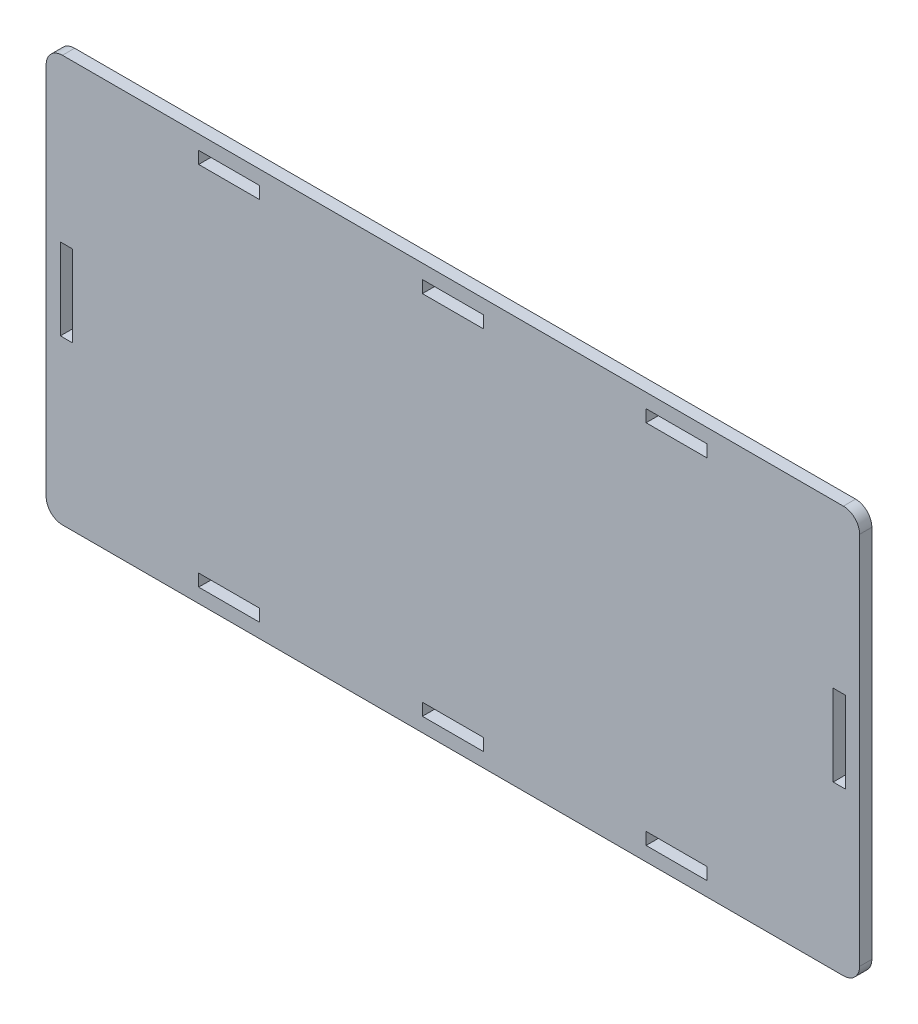
SolidWorks part; units mm, degrees
ref_plane "Front Plane" through (0, 0, 0) normal (0, 0, 1) x (1, 0, 0)
ref_plane "Top Plane" through (0, 0, 0) normal (0, 1, 0) x (1, 0, 0)
ref_plane "Right Plane" through (0, 0, 0) normal (1, 0, 0) x (0, 0, -1)
sketch "Sketch1" plane through (0, 0, 0) normal (0, 0, 1) x (1, 0, 0)
  line L1 (-96, 50) -> (96, 50)
  line L2 (-100, 46) -> (-100, -46)
  line L3 (-96, -50) -> (96, -50)
  line L4 (100, 46) -> (100, -46)
  line L5 (-100, 50) -> (100, -50) construction
  line L6 (-100, -50) -> (100, 50) construction
  arc A0 (96, 50) -> (100, 46) centre (96, 46) cw
  arc A1 (100, -46) -> (96, -50) centre (96, -46) cw
  arc A2 (-96, -50) -> (-100, -46) centre (-96, -46) cw
  arc A3 (-100, 46) -> (-96, 50) centre (-96, 46) cw
  point P0 (0, 0)
  dimension "D3" = 4
  dimension "D1" = 200
  dimension "D2" = 100
extrude "Boss-Extrude2" add sketch "Sketch1" along normal blind 3
sketch "Sketch3" plane through (0, 0, 3) normal (0, 0, 1) x (1, 0, 0)
  line L0 (0, 50) -> (0, -50) construction
  line L1 (-95, 45) -> (95, 45) construction
  line L2 (-95, 45) -> (-95, -45) construction
  line L3 (-95, -45) -> (95, -45) construction
  line L4 (95, 45) -> (95, -45) construction
  line L5 (-95, 45) -> (95, -45) construction
  line L6 (-95, -45) -> (95, 45) construction
  line L7 (-62.5, 46.5) -> (-47.5, 46.5)
  line L8 (-62.5, 46.5) -> (-62.5, 43.5)
  line L9 (-62.5, 43.5) -> (-47.5, 43.5)
  line L10 (-47.5, 46.5) -> (-47.5, 43.5)
  line L11 (-62.5, 46.5) -> (-47.5, 43.5) construction
  line L12 (-62.5, 43.5) -> (-47.5, 46.5) construction
  line L13 (96, 50) -> (-96, 50) construction
  line L14 (-96, -50) -> (96, -50) construction
  line L15 (100, 0) -> (-100, 0) construction
  line L16 (100, -46) -> (100, 46) construction
  line L17 (-100, 46) -> (-100, -46) construction
  line L22 (62.5, 43.5) -> (47.5, 43.5)
  line L23 (-7.5, 46.5) -> (7.5, 46.5)
  line L24 (-7.5, 46.5) -> (-7.5, 43.5)
  line L25 (-7.5, 43.5) -> (7.5, 43.5)
  line L26 (7.5, 46.5) -> (7.5, 43.5)
  line L27 (-7.5, 46.5) -> (7.5, 43.5) construction
  line L28 (-7.5, 43.5) -> (7.5, 46.5) construction
  line L29 (-96.5, 10) -> (-93.5, 10)
  line L30 (-96.5, 10) -> (-96.5, -10)
  line L31 (-96.5, -10) -> (-93.5, -10)
  line L32 (-93.5, 10) -> (-93.5, -10)
  line L33 (-96.5, 10) -> (-93.5, -10) construction
  line L34 (-96.5, -10) -> (-93.5, 10) construction
  line L35 (47.5, 46.5) -> (47.5, 43.5)
  line L36 (62.5, 46.5) -> (47.5, 46.5)
  line L37 (62.5, 46.5) -> (62.5, 43.5)
  line L38 (-62.5, -43.5) -> (-47.5, -43.5)
  line L39 (-47.5, -46.5) -> (-47.5, -43.5)
  line L40 (-62.5, -46.5) -> (-47.5, -46.5)
  line L41 (-62.5, -46.5) -> (-62.5, -43.5)
  line L42 (-7.5, -43.5) -> (7.5, -43.5)
  line L43 (7.5, -46.5) -> (7.5, -43.5)
  line L44 (-7.5, -46.5) -> (7.5, -46.5)
  line L45 (-7.5, -46.5) -> (-7.5, -43.5)
  line L46 (62.5, -46.5) -> (62.5, -43.5)
  line L47 (62.5, -46.5) -> (47.5, -46.5)
  line L48 (47.5, -46.5) -> (47.5, -43.5)
  line L49 (62.5, -43.5) -> (47.5, -43.5)
  line L50 (96.5, -10) -> (93.5, -10)
  line L51 (93.5, 10) -> (93.5, -10)
  line L52 (96.5, 10) -> (93.5, 10)
  line L53 (96.5, 10) -> (96.5, -10)
  point P0 (0, 0)
  point P5 (-55, 45)
  point P23 (0, 45)
  point P28 (-95, 0)
  dimension "D1" = 190
  dimension "D2" = 90
  dimension "D3" = 15
  dimension "D4" = 3
  dimension "D5" = 40
  dimension "D6" = 15
  dimension "D7" = 3
  dimension "D8" = 3
  dimension "D9" = 20
extrude "Cut-Extrude1" cut sketch "Sketch3" against normal blind 3
